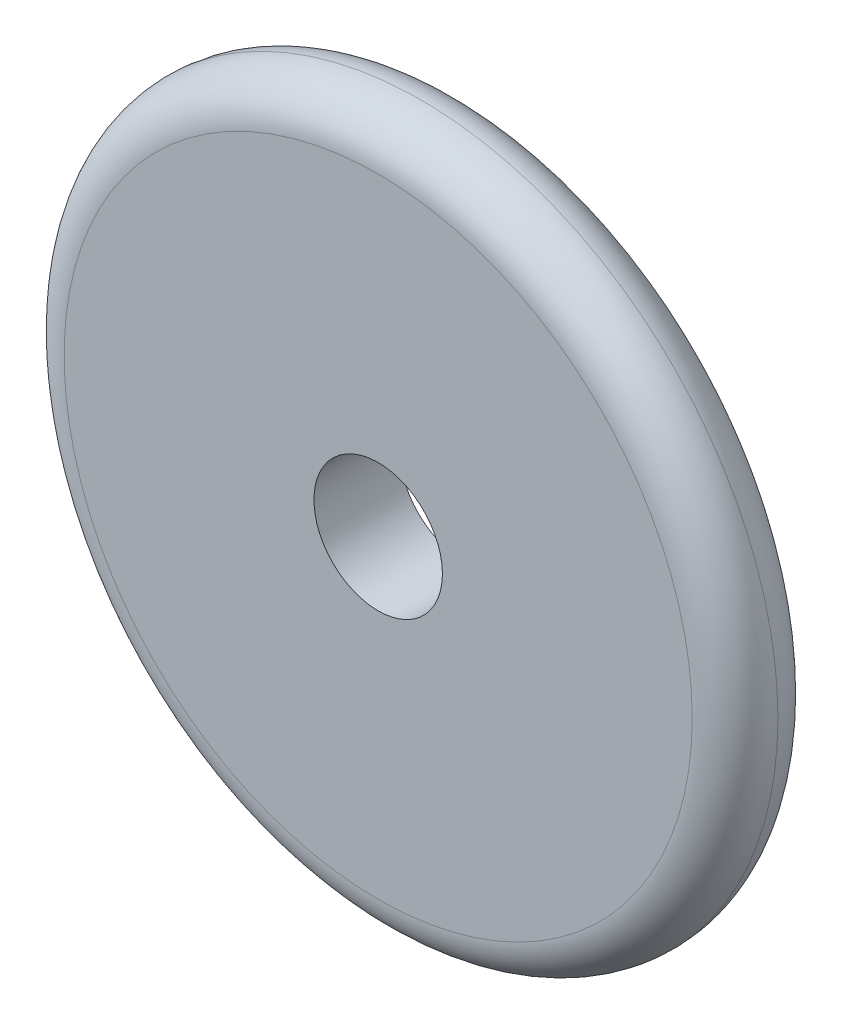
SolidWorks part; units mm, degrees
ref_plane "Front Plane" through (0, 0, 0) normal (0, 0, 1) x (1, 0, 0)
ref_plane "Top Plane" through (0, 0, 0) normal (0, 1, 0) x (1, 0, 0)
ref_plane "Right Plane" through (0, 0, 0) normal (1, 0, 0) x (0, 0, -1)
sketch "Sketch1" plane through (0, 0, 0) normal (0, 0, 1) x (1, 0, 0)
  circle A0 centre (0, 0) radius 125
  dimension "D1" = 250
extrude "Boss-Extrude1" add sketch "Sketch1" along normal blind 30
fillet "Fillet1" radius 15 2 edges at (125, 0, 0) (125, 0, 30)
sketch "Sketch2" plane through (0, 0, 30) normal (0, 0, 1) x (1, 0, 0)
  circle A0 centre (0, 0) radius 22.5
  dimension "D1" = 45
extrude "Cut-Extrude1" cut sketch "Sketch2" against normal blind 30
